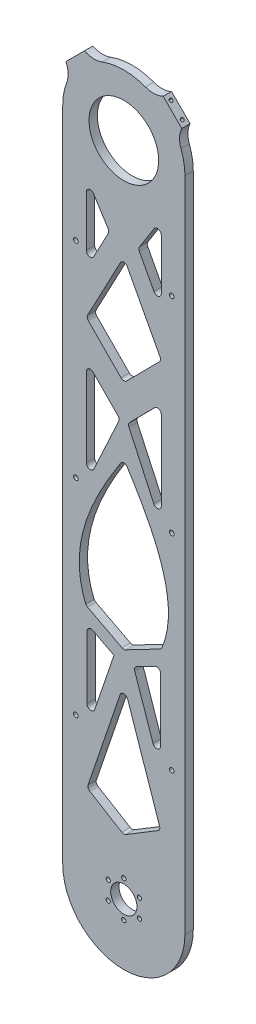
SolidWorks part; units mm, degrees
material "1060 Alloy"
ref_plane "Front Plane" through (0, 0, 0) normal (0, 0, 1) x (1, 0, 0)
ref_plane "Top Plane" through (0, 0, 0) normal (0, 1, 0) x (1, 0, 0)
ref_plane "Right Plane" through (0, 0, 0) normal (1, 0, 0) x (0, 0, -1)
sketch "Sketch2" plane through (0, 0, 0) normal (0, 0, 1) x (1, 0, 0)
  line L0 (0, 0) -> (0, 500) construction
  line L1 (-46.5, 0) -> (-46.5, 500)
  line L2 (46.5, 0) -> (46.5, 500)
  arc A0 (-46.5, 0) -> (46.5, 0) centre (0, 0) ccw
  arc A1 (46.5, 500) -> (-46.5, 500) centre (0, 500) ccw
  circle A2 centre (0, 500) radius 37.25 construction
  circle A3 centre (0, 0) radius 10
  circle A4 centre (0, 13.75) radius 1.65
  circle A5 centre (0, 0) radius 13.75 construction
  circle A6 centre (11.9078, 6.875) radius 1.65
  circle A7 centre (11.9078, -6.875) radius 1.65
  circle A8 centre (0, -13.75) radius 1.65
  circle A9 centre (-11.9078, -6.875) radius 1.65
  circle A10 centre (-11.9078, 6.875) radius 1.65
  point P3 (0, 250)
  point P27 (0, 0)
  dimension "D2" = 74.5
  dimension "D4" = 20
  dimension "D5" = 3.3
  dimension "D6" = 27.5
  dimension "D3" = 46.5
  dimension "D1" = 500
  dimension "D7" = 6
extrude "Boss-Extrude1" add sketch "Sketch2" along normal blind 6.35
sketch "Sketch4" plane through (0, 0, 6.35) normal (0, 0, 1) x (1, 0, 0)
  line L0 (0, 500) -> (0, 999.1647) construction
  line L29 (46.5, 500) -> (-46.5, 500) construction
  line L31 (28.0053, 59.376) -> (0, 42.4117)
  line L32 (0, 141.6934) -> (28.0053, 59.376)
  line L33 (-28.0053, 59.376) -> (0, 141.6934)
  line L34 (0, 42.4117) -> (-28.0053, 59.376)
  line L35 (-7.5, 156.9059) -> (-28.0053, 96.6336)
  line L36 (-28.0053, 167.5829) -> (-7.5, 156.9059)
  line L37 (-28.0053, 96.6336) -> (-28.0053, 167.5829)
  line L38 (28.0053, 167.5829) -> (7.5, 156.9059)
  line L39 (28.0053, 96.6336) -> (28.0053, 167.5829)
  line L40 (7.5, 156.9059) -> (28.0053, 96.6336)
  line L41 (0, 164.2751) -> (28.5505, 179.1412)
  line L42 (0, 164.2751) -> (-28.5505, 179.1412)
  line L43 (28.5505, 259.5868) -> (3, 314.9383)
  line L44 (28.5505, 340.7931) -> (28.5505, 259.5868)
  line L45 (3, 314.9383) -> (28.5505, 340.7931)
  line L46 (-3, 314.9383) -> (-28.5505, 340.7931)
  line L47 (-28.5505, 259.5868) -> (-3, 314.9383)
  line L48 (-28.5505, 340.7931) -> (-28.5505, 259.5868)
  line L49 (0, 423.1428) -> (-28.5505, 369.2462)
  line L50 (-28.5505, 369.2462) -> (0, 340.3557)
  line L51 (0, 340.3557) -> (28.5505, 369.2462)
  line L52 (0, 423.1428) -> (28.5505, 369.2462)
  line L53 (-28.5505, 462.0952) -> (-28.5505, 401.2902)
  line L54 (-11, 434.4215) -> (-28.5505, 462.0952)
  line L55 (-28.5505, 401.2902) -> (-11, 434.4215)
  line L56 (28.5505, 401.2902) -> (11, 434.4215)
  line L57 (28.5505, 462.0952) -> (28.5505, 401.2902)
  line L58 (11, 434.4215) -> (28.5505, 462.0952)
  arc A0 (46.5, 500) -> (-46.5, 500) centre (0, 500) ccw construction
  arc A1 (46.5, 500) -> (-46.5, 500) centre (0, 500) ccw construction
  spline S2 degree 3 poles (28.5505, 179.1412) (45.3203, 216.9857) (19.4301, 259.7903) (0, 290.0258) knots 0 0 0 0 1 1 1 1
  spline S3 degree 3 poles (-28.5505, 179.1412) (-45.3203, 216.9857) (-19.4301, 259.7903) (0, 290.0258) knots 0 0 0 0 1 1 1 1
extrude "Cut-Extrude1" cut sketch "Sketch4" against normal blind 10
fillet "Fillet3" radius 3 29 edges at (-11, 434.4215, 3.175) (-28.5505, 401.2902, 3.175) (28.5505, 401.2902, 3.175) (11, 434.4215, 3.175) (28.5505, 462.0952, 3.175) (-28.5505, 462.0952, 3.175) (0, 423.1428, 3.175) (-28.5505, 369.2462, 3.175) (28.5505, 369.2462, 3.175) (0, 340.3557, 3.175) (28.5505, 340.7931, 3.175) (-28.5505, 340.7931, 3.175) (-3, 314.9383, 3.175) (3, 314.9383, 3.175) (28.5505, 259.5868, 3.175) (-28.5505, 259.5868, 3.175) (28.5505, 179.1412, 3.175) (0, 290.0258, 3.175) (-28.5505, 179.1412, 3.175) (0, 164.2751, 3.175) (-28.0053, 96.6336, 3.175) (28.0053, 96.6336, 3.175) (7.5, 156.9059, 3.175) (-28.0053, 167.5829, 3.175) (28.0053, 167.5829, 3.175) (0, 141.6934, 3.175) (28.0053, 59.376, 3.175) (-28.0053, 59.376, 3.175) (0, 42.4117, 3.175)
sketch "Sketch5" plane through (0, 0, 6.35) normal (0, 0, 1) x (1, 0, 0)
  line L0 (0, -46.5) -> (108.8395, -46.5) construction
  line L1 (46.5, 100) -> (-46.5, 100) construction
  line L2 (46.5, 0) -> (46.5, 500) construction
  line L3 (-46.5, 500) -> (-46.5, 0) construction
  line L4 (-46.5, 106.35) -> (46.5, 106.35) construction
  line L5 (36.5, 106.35) -> (36.5, 100) construction
  line L6 (0, 106.35) -> (0, 100) construction
  line L7 (-46.5, 256.35) -> (46.5, 256.35) construction
  line L8 (-46.5, 181.35) -> (46.5, 181.35) construction
  line L9 (-46.5, 337.7) -> (46.5, 337.7) construction
  arc A1 (-46.5, 0) -> (46.5, 0) centre (0, 0) ccw construction
  circle A2 centre (36.5, 103.175) radius 1.75
  circle A3 centre (-36.5, 103.175) radius 1.75
  circle A4 centre (36.5, 259.525) radius 1.75
  circle A5 centre (-36.5, 259.525) radius 1.75
  circle A6 centre (36.5, 415.875) radius 1.75
  circle A7 centre (-36.5, 415.875) radius 1.75
  point P18 (36.5, 103.175)
  dimension "D2" = 3.5
  dimension "D1" = 146.5
  dimension "D3" = 10
  dimension "D4" = 6.35
  dimension "D5" = 150
  dimension "D6" = 81.35
  dimension "D7" = 81.35
extrude "Cut-Extrude2" cut sketch "Sketch5" against normal through all
sketch "Sketch6" plane through (0, 0, 6.35) normal (0, 0, 1) x (1, 0, 0)
  circle A0 centre (0, 500) radius 26.5
  arc A1 (46.5, 500) -> (-46.5, 500) centre (0, 500) ccw construction
  arc A2 (46.5, 500) -> (-46.5, 500) centre (0, 500) ccw construction
  dimension "D1" = 20
extrude "Cut-Extrude3" cut sketch "Sketch6" against normal blind 10
sketch "Sketch7" plane through (0, 0, 6.35) normal (0, 0, 1) x (1, 0, 0)
  line L1 (40.0163, 523.6842) -> (44.1104, 529.9682) construction
  line L2 (23.6842, 540.0163) -> (29.9682, 544.1104) construction
  line L3 (44.1104, 529.9682) -> (29.9682, 544.1104)
  line L4 (0, 500) -> (37.0393, 537.0393) construction
  line L5 (0, 500) -> (0, 546.5) construction
  arc A0 (46.5, 500) -> (-46.5, 500) centre (0, 500) ccw construction
  arc A1 (29.9682, 544.1104) -> (16.4747, 543.4837) centre (22.4977, 559.381) cw
  arc A2 (44.1104, 529.9682) -> (43.4837, 516.4747) centre (59.381, 522.4977) ccw
  arc A3 (16.4747, 543.4837) -> (43.4837, 516.4747) centre (0, 500) cw
  dimension "D3" = 17
  dimension "D5" = 17
  dimension "D1" = 20
  dimension "D2" = 7.5
  dimension "D4" = 8
  dimension "D6" = 8
  dimension "D7" = 45
extrude "Boss-Extrude2" add sketch "Sketch7" against normal up to surface (6.35 mm away) up to face at (26.5, 500, 0)
sketch "Sketch8" plane through (287.0393, 287.0393, 0) normal (0.7071, 0.7071, 0) x (0, 0, -1)
  line L0 (0, 363.5534) -> (-6.35, 363.5534) construction
  line L1 (0, 343.5534) -> (-6.35, 343.5534) construction
  line L2 (-6.35, 343.5534) -> (-6.35, 363.5534) construction
  point P0 (-3.175, 359.5534)
  point P1 (-3.175, 347.5534)
  dimension "D1" = 4
  dimension "D2" = 4
  dimension "D3" = 3.175
hole_wizard "Tap Drill for M3x0.5 Tap1" positions "Sketch8" profile "Sketch9" hole size "M3x0.5" standard "ANSI Metric"
sketch "Sketch9" plane through (32.7967, 541.282, 3.175) normal (0, 0, 1) x (-0.7071, 0.7071, 0)
  line L0 (0, 0) -> (0, 5.7511)
  line L1 (0, 5.7511) -> (1.25, 5)
  line L2 (1.25, 5) -> (1.25, 0)
  line L5 (1.25, 0) -> (0, 0)
  line L10 (0, 5.7511) -> (-1.25, 5) construction
  line L11 (0, -6.35) -> (0, 107.95) construction
  dimension "Hole Dia." = 2.5
  dimension "Hole Depth" = 5
  dimension "Drill Angle" = 118
pattern_circular "CirPattern2" count 2 every 90 about axis through (0, 500, -3.65) along (0, 0, 1) of "Boss-Extrude2", "Tap Drill for M3x0.5 Tap1"
equation "\"L1L\"=500"
equation "\"L1Thick\"=6.35"
equation "\"D1@Sketch2\"=\"L1L\""
equation "\"Harm-Drive-Outer\"=74.5"
equation "\"D2@Sketch2\"=\"Harm-Drive-Outer\""
equation "\"D1@Boss-Extrude1\"=\"L1Thick\""
